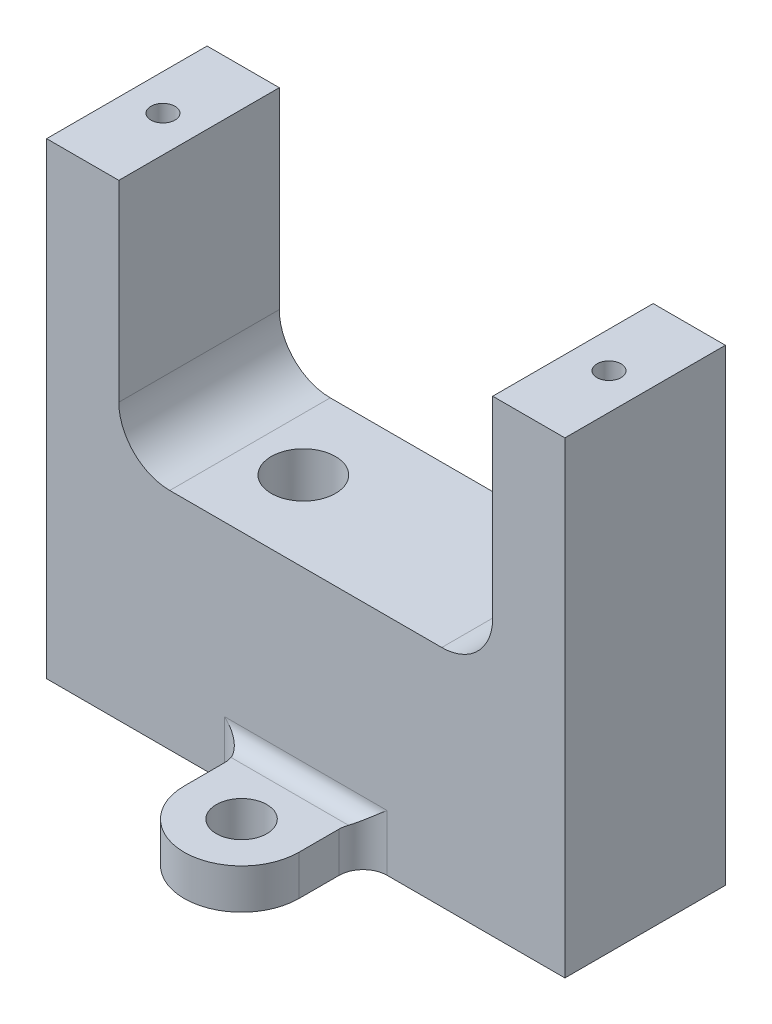
SolidWorks part; units mm, degrees
ref_plane "Front Plane" through (0, 0, 0) normal (0, 0, 1) x (1, 0, 0)
ref_plane "Top Plane" through (0, 0, 0) normal (0, 1, 0) x (1, 0, 0)
ref_plane "Right Plane" through (0, 0, 0) normal (1, 0, 0) x (0, 0, -1)
sketch "Sketch1" plane through (0, 0, 0) normal (0, 1, 0) x (1, 0, 0)
  line L0 (-16.15, 5) -> (-11.65, -5) construction
  line L1 (-16.15, 5) -> (-11.65, 5)
  line L2 (-16.15, 5) -> (-16.15, -5)
  line L3 (-16.15, -5) -> (-11.65, -5)
  line L4 (-11.65, 5) -> (-11.65, -5)
  line L5 (0, 0) -> (0, -5) construction
  line L6 (0, -5) -> (-11.65, -5) construction
  line L7 (16.15, 5) -> (11.65, -5) construction
  line L8 (11.65, 5) -> (11.65, -5)
  line L9 (16.15, -5) -> (11.65, -5)
  line L10 (16.15, 5) -> (16.15, -5)
  line L11 (16.15, 5) -> (11.65, 5)
  circle A0 centre (-13.9, 0) radius 0.75 construction
  circle A2 centre (13.9, 0) radius 0.75 construction
  dimension "D1" = 1.5
  dimension "D2" = 13.9
  dimension "D3" = 10
  dimension "D4" = 4.5
extrude "Boss-Extrude1" add sketch "Sketch1" against normal blind 15.15
hole_wizard "Ø1.5 (1.5) Diameter Hole1" positions "Sketch3" profile "Sketch4" hole size "Ø1.5" standard "ANSI Metric"
sketch "Sketch3" plane through (0, 0, 0) normal (0, 1, 0) x (1, 0, 0)
  line L0 (16.15, 5) -> (11.65, -5) construction
  point P0 (-13.9, 0)
  point P3 (13.9, 0)
sketch "Sketch4" plane through (-13.9, 0, 0) normal (1, 0, 0) x (0, 0, 1)
  line L0 (0, 0) -> (0, 8)
  line L1 (0, 8) -> (0.75, 7.5494)
  line L2 (0.75, 7.5494) -> (0.75, 0)
  line L5 (0.75, 0) -> (0, 0)
  line L10 (0, 8) -> (-0.75, 7.5494) construction
  line L11 (0, -6.35) -> (0, 107.95) construction
  dimension "Hole Dia." = 1.5
  dimension "Hole Depth" = 8
  dimension "Drill Angle" = 118
sketch "Sketch5" plane through (0, -15.15, 0) normal (0, -1, 0) x (1, 0, 0)
  line L4 (-16.15, 5) -> (-16.15, -5)
  line L5 (-16.15, -5) -> (-11.65, -5)
  line L6 (-11.65, -5) -> (-11.65, 5)
  line L7 (-11.65, 5) -> (-16.15, 5)
  line L8 (-16.15, 5) -> (-16.15, -5)
  line L9 (-16.15, -5) -> (16.15, -5)
  line L11 (16.15, 5) -> (-16.15, 5)
  line L12 (11.65, -5) -> (16.15, -5)
  line L13 (16.15, -5) -> (16.15, 5)
  line L14 (16.15, 5) -> (11.65, 5)
  line L15 (11.65, 5) -> (11.65, -5)
  line L17 (16.15, -5) -> (16.15, 5)
  circle A0 centre (-5.15, 0) radius 2
  circle A1 centre (-13.9, 0) radius 0.75 construction
  dimension "D1" = 4
  dimension "D2" = 8.75
  dimension "D3" = 0
  dimension "D4" = 0
extrude "Boss-Extrude2" add sketch "Sketch5" along normal blind 14
fillet "Fillet1" radius 3.175 2 edges at (11.65, -15.15, 0) (-11.65, -15.15, 0)
sketch "Sketch6" plane through (-16.15, 0, 0) normal (-1, 0, 0) x (0, 0, 1)
  line L0 (5, -15.15) -> (-5, -15.15) construction
  line L1 (5, -15.15) -> (-5, -15.15) construction
  circle A0 centre (-1.2, -20.65) radius 2
  dimension "D1" = 4
  dimension "D2" = 5.5
  dimension "D3" = 1.2
extrude "Cut-Extrude1" cut sketch "Sketch6" against normal blind 15.4
sketch "Sketch7" plane through (0, -29.15, 0) normal (0, -1, 0) x (1, 0, 0)
  line L0 (-16.15, -5) -> (16.15, -5) construction
  line L1 (16.15, 5) -> (-16.15, 5) construction
  line L2 (-3.575, -5) -> (3.575, -5)
  line L3 (3.575, 5) -> (-3.575, 5)
  line L4 (0, 0) -> (16.15, 0) construction
  line L5 (16.15, -5) -> (16.15, 5) construction
  line L6 (-3.575, 9) -> (-3.575, 5)
  line L7 (3.575, 9) -> (3.575, 5)
  line L8 (3.575, -5) -> (-3.575, -5)
  line L9 (3.575, -9) -> (3.575, -5)
  line L10 (-3.575, -9) -> (-3.575, -5)
  circle A0 centre (0, 9) radius 1.575
  arc A1 (3.575, 9) -> (-3.575, 9) centre (0, 9) ccw
  circle A2 centre (0, 9) radius 3.575 construction
  circle A3 centre (0, -9) radius 1.575
  arc A4 (3.575, -9) -> (-3.575, -9) centre (0, -9) cw
  line M6 (-16.15, -5) -> (16.15, -5)
  dimension "D1" = 3.15
  dimension "D2" = 2
  dimension "D3" = 4
extrude "Boss-Extrude3" add sketch "Sketch7" against normal blind 2.5 contours L7 A1 L6 L3 A0 | A4 L9 L10 A3 M6 region at (0, -29.15, -5.1042) region at (0, -29.15, 5.1042)
fillet "Fillet3" radius 1.5 4 edges at (3.575, -27.9, -5) (-3.575, -27.9, -5) (-3.575, -27.9, 5) (3.575, -27.9, 5)
fillet "Fillet4" radius 1 2 edges at (0, -26.65, 5) (0, -26.65, -5)
